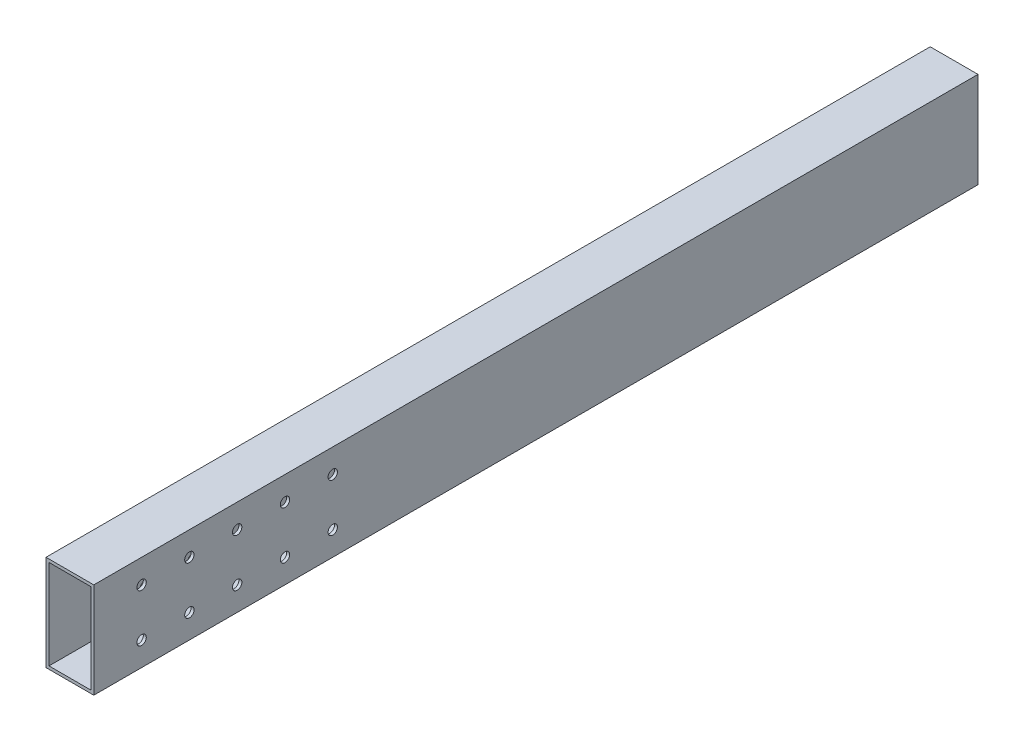
SolidWorks part; units mm, degrees
material "6061-T4 (SS)"
ref_plane "Front Plane" through (0, 0, 0) normal (0, 0, 1) x (1, 0, 0)
ref_plane "Top Plane" through (0, 0, 0) normal (0, 1, 0) x (1, 0, 0)
ref_plane "Right Plane" through (0, 0, 0) normal (1, 0, 0) x (0, 0, -1)
sketch "Sketch1" plane through (0, 0, 0) normal (0, 0, 1) x (1, 0, 0)
  line L0 (1.5875, 49.2125) -> (23.8125, 49.2125)
  line L5 (0, 0) -> (25.4, 0)
  line L6 (0, 0) -> (0, 50.8)
  line L7 (0, 50.8) -> (25.4, 50.8)
  line L8 (25.4, 0) -> (25.4, 50.8)
  line L13 (23.8125, 1.5875) -> (23.8125, 49.2125)
  line L14 (1.5875, 1.5875) -> (23.8125, 1.5875)
  line L15 (1.5875, 1.5875) -> (1.5875, 49.2125)
  dimension "D1" = 25.4
  dimension "D2" = 1.5875
  dimension "D3" = 50.8
extrude "Boss-Extrude1" add sketch "Sketch1" along normal blind 469.9
sketch "Sketch2" plane through (25.4, 0, 0) normal (-1, 0, 0) x (0, 0, 1)
  line L0 (469.9, 50.8) -> (469.9, 0) construction
  line L1 (469.9, 50.8) -> (0, 50.8) construction
  circle A16 centre (419.1, 38.1) radius 2.4892
  circle A17 centre (393.7, 38.1) radius 2.4892
  circle A18 centre (368.3, 38.1) radius 2.4892
  circle A19 centre (342.9, 38.1) radius 2.4892
  circle A21 centre (419.1, 12.7) radius 2.4892
  circle A22 centre (393.7, 12.7) radius 2.4892
  circle A23 centre (368.3, 12.7) radius 2.4892
  circle A24 centre (342.9, 12.7) radius 2.4892
  circle A26 centre (444.5, 12.7) radius 2.4892
  circle A29 centre (444.5, 38.1) radius 2.4892
  circle A30 centre (317.5, 38.1) radius 2.4892 [skipped]
  circle A31 centre (317.5, 12.7) radius 2.4892 [skipped]
  point P2 (0, 0)
  point P14 (0, 0)
  dimension "D4" = 25.4
  dimension "D5" = 6
  dimension "D6" = 2
  dimension "D1" = 4.9784
  dimension "D7" = 12.7
  dimension "D2" = 25.4
  dimension "D3" = 25.4
extrude "Cut-Extrude1" cut sketch "Sketch2" along normal up to next contours A24 | A23 | A18 | A19
sketch "Sketch3" plane through (0, 0, 0) normal (-1, 0, 0) x (0, 0, 1)
  line L0 (469.9, 25.4) -> (0, 25.4) construction
  line L1 (469.9, 50.8) -> (469.9, 0) construction
  line L2 (0, 50.8) -> (0, 0) construction
  line L4 (88.9, 44.45) -> (139.7, 44.45) construction
  line L5 (88.9, 44.45) -> (88.9, 6.35) construction
  line L6 (88.9, 6.35) -> (139.7, 6.35) construction
  line L7 (139.7, 44.45) -> (139.7, 6.35) construction
  line L8 (88.9, 44.45) -> (139.7, 6.35) construction
  line L9 (88.9, 6.35) -> (139.7, 44.45) construction
  circle A0 centre (114.3, 25.4) radius 14.2875
  circle A1 centre (139.7, 44.45) radius 2.4892
  circle A2 centre (88.9, 44.45) radius 2.4892
  circle A3 centre (88.9, 6.35) radius 2.4892
  circle A4 centre (139.7, 6.35) radius 2.4892
  dimension "D1" = 28.575
  dimension "D2" = 114.3
  dimension "D5" = 4.9784
  dimension "D3" = 19.05
  dimension "D4" = 25.4
extrude "Cut-Extrude2" cut sketch "Sketch3" against normal up to next
extrude "Cut-Extrude5" cut sketch "Sketch2<3>" along normal through all contours A22 | A17 | A26 | A29 | A16 | A21 region at (25.4, 38.1, 419.1) region at (25.4, 38.1, 393.7) region at (25.4, 12.7, 419.1) region at (25.4, 12.7, 393.7) region at (25.4, 12.7, 444.5) region at (25.4, 38.1, 444.5)
sketch "Sketch2<3>" plane through (25.4, 0, 0) normal (-1, 0, 0) x (0, 0, 1) same geometry as "Sketch2"
